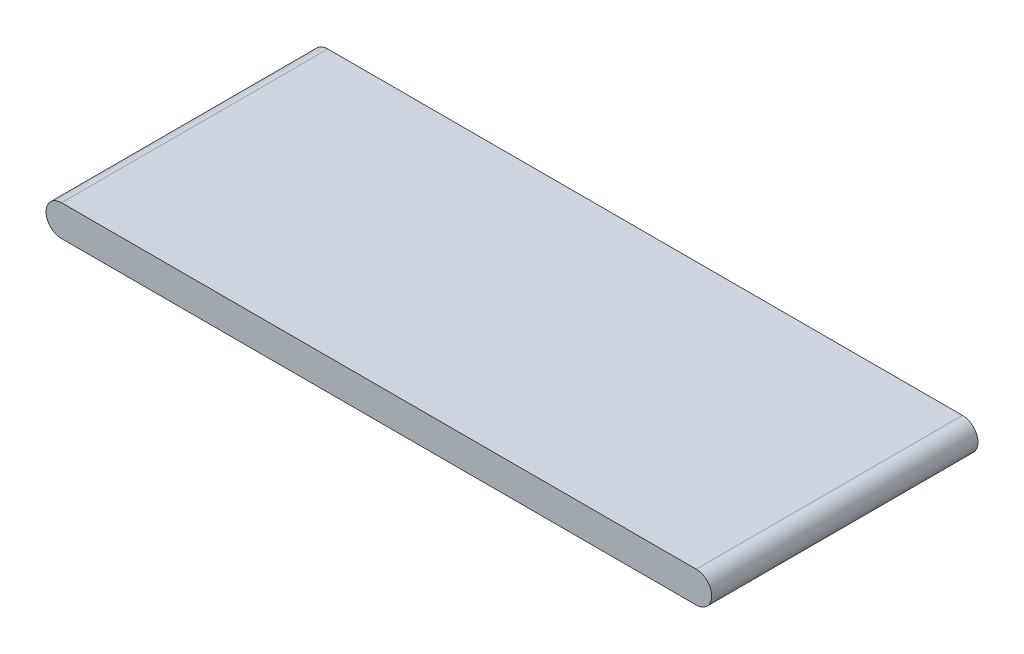
SolidWorks part; units mm, degrees
ref_plane "Front" through (0, 0, 0) normal (0, 0, 1) x (1, 0, 0)
ref_plane "Top" through (0, 0, 0) normal (0, 1, 0) x (1, 0, 0)
ref_plane "Right" through (0, 0, 0) normal (1, 0, 0) x (0, 0, -1)
sketch "Sketch1" plane through (0, 0, 0) normal (0, 0, 1) x (1, 0, 0)
  line L0 (-715, 0) -> (715, 0)
  line L1 (0, 72.5805) -> (0, -67.8405) construction
  line L2 (-715, -70) -> (715, -70)
  arc A0 (-715, 0) -> (-715, -70) centre (-715, -35) ccw
  arc A1 (715, 0) -> (715, -70) centre (715, -35) cw
  dimension "D1" = 35
  dimension "D2" = 1500
extrude "Boss-Extrude1" add sketch "Sketch1" along normal mid plane 600
